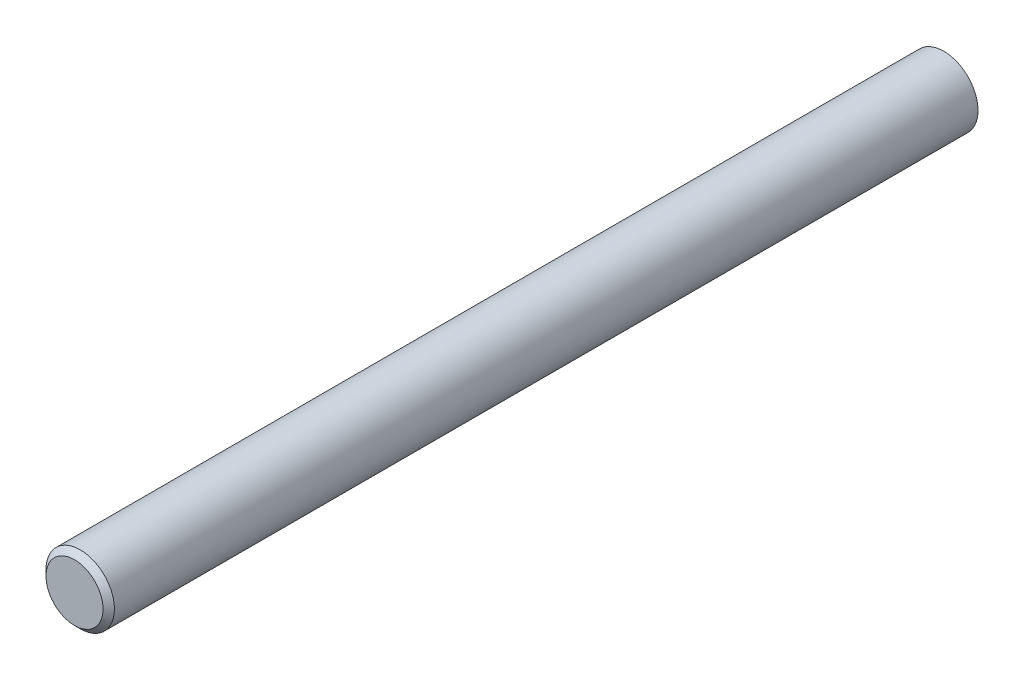
SolidWorks part; units mm, degrees
ref_plane "Ebene vorne" through (0, 0, 0) normal (0, 0, 1) x (1, 0, 0)
ref_plane "Ebene oben" through (0, 0, 0) normal (0, 1, 0) x (1, 0, 0)
ref_plane "Ebene rechts" through (0, 0, 0) normal (1, 0, 0) x (0, 0, -1)
sketch "Skizze1" plane through (0, 0, 0) normal (1, 0, 0) x (0, 0, -1)
  line L0 (7, 3) -> (2, 3) construction
  line L1 (54.2175, 3) -> (54.2175, 0) construction
  line L2 (0, 0) -> (99, 0) construction
  line L3 (7, 3) -> (54.2175, 3) construction
  line L4 (-22, 0) -> (0, 0) construction
  line L5 (-22, 3) -> (-22, 0) construction
  line L6 (2, 3) -> (-22, 3) construction
  line L7 (7, 3) -> (2, 3)
  line L8 (54.2175, 3) -> (54.2175, 0)
  line L9 (0, 0) -> (54.2175, 0)
  line L10 (7, 3) -> (54.2175, 3)
  line L11 (-22, 0) -> (0, 0)
  line L12 (-22, 3) -> (-22, 0)
  line L13 (2, 3) -> (-22, 3)
revolve "Rotation1" add sketch "Skizze1" angle 360 about L11
chamfer "Fase1" distance 0.5 angle 45 1 edges at (0, -3, 22)
